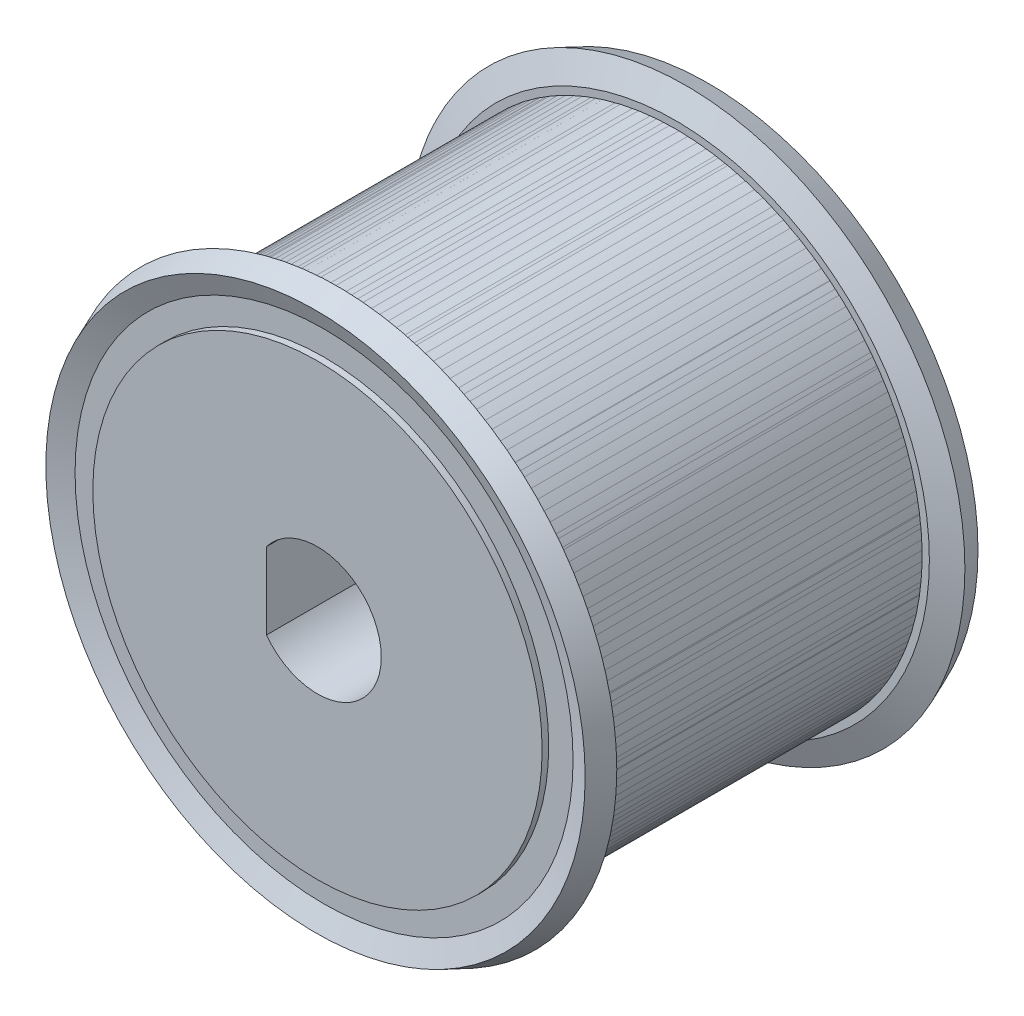
SolidWorks part; units mm, degrees
ref_plane "前视基准面" through (0, 0, 0) normal (0, 0, 1) x (1, 0, 0)
ref_plane "上视基准面" through (0, 0, 0) normal (0, 1, 0) x (1, 0, 0)
ref_plane "右视基准面" through (0, 0, 0) normal (1, 0, 0) x (0, 0, -1)
ref_axis "基准轴1" through (0, 0, 55) along (0, 0, -1)
sketch "SketchRevolveGearBelt01" plane through (0, 0, 0) normal (1, 0, 0) x (0, 0, -1)
  line L0 (0, 0) -> (1, 0) construction
  line L1 (15.24, 0) -> (15.24, 17.6084)
  line L2 (15.24, 17.6084) -> (14.7244, 17.6084)
  line L3 (14.7244, 17.6084) -> (14.7244, 19.5169)
  line L4 (14.7244, 19.5169) -> (15.3953, 21.1368)
  line L5 (15.3953, 21.1368) -> (13.6424, 21.8629)
  line L6 (13.6424, 21.8629) -> (12.827, 19.8944)
  line L7 (12.827, 19.8944) -> (12.827, 19.3229)
  line L8 (12.827, 19.3229) -> (-12.827, 19.3229)
  line L9 (-12.827, 19.3229) -> (-12.827, 19.8944)
  line L10 (-12.827, 19.8944) -> (-13.6424, 21.8629)
  line L11 (-13.6424, 21.8629) -> (-15.3953, 21.1368)
  line L12 (-15.3953, 21.1368) -> (-14.7244, 19.5169)
  line L13 (-14.7244, 19.5169) -> (-14.7244, 17.6084)
  line L14 (-14.7244, 17.6084) -> (-15.24, 17.6084)
  line L15 (-15.24, 17.6084) -> (-15.24, 0)
  line L16 (-15.24, 0) -> (15.24, 0)
  dimension "GearBeltFlange1OutsideLength" = 1.9086
  dimension "GearBeltFlange1X" = 0.6709
  dimension "GearBeltFlange1Y" = 1.6198
  dimension "GearBeltFlangeThickness" = 1.8974
  dimension "GearBeltFlangeInside" = 0.5715
  dimension "GearBeltOutsideDiameter" = 19.3229
  dimension "GearBeltFlange2X" = 0.6709
revolve "GearBelt01" add sketch "SketchRevolveGearBelt01" angle 360 about L0
sketch "SketchToothGearBelt01" plane through (0, 0, 0) normal (0, 0, 1) x (1, 0, 0)
  arc A0 (19.2019, 2.1549) -> (19.2019, -2.1549) centre (0, 0) cw
  spline S0 degree 3 poles (19.2019, -2.1549) (19.2051, -2.1266) (19.2062, -2.0838) (19.2007, -2.0271) (19.1929, -1.985) (19.1817, -1.9438) (19.167, -1.9037) (19.149, -1.8649) (19.1278, -1.8278) (19.1036, -1.7926) (19.0765, -1.7596) (19.0468, -1.7289) (19.0145, -1.7009) (18.9801, -1.6756) (18.9436, -1.6534) (18.9054, -1.6342) (18.8657, -1.6184) (18.8248, -1.6059) (18.7831, -1.597) (18.7407, -1.5914) (18.6735, -1.5892) (18.5873, -1.5911) (18.4822, -1.5873) (18.3832, -1.5753) (18.2854, -1.5557) (18.1895, -1.5285) (18.096, -1.4939) (18.0055, -1.452) (17.9186, -1.4032) (17.8357, -1.3477) (17.7575, -1.2859) (17.6843, -1.2181) (17.6167, -1.1449) (17.5551, -1.0665) (17.4997, -0.9836) (17.4511, -0.8965) (17.4094, -0.806) (17.3749, -0.7124) (17.3478, -0.6164) (17.3285, -0.5186) (17.3165, -0.4196) (17.313, -0.2999) (17.3145, -0.16) (17.3139, 0) (17.3145, 0.16) (17.313, 0.2999) (17.3165, 0.4196) (17.3285, 0.5186) (17.3478, 0.6164) (17.3749, 0.7124) (17.4094, 0.806) (17.4511, 0.8965) (17.4997, 0.9836) (17.5551, 1.0665) (17.6167, 1.1449) (17.6843, 1.2181) (17.7575, 1.2859) (17.8357, 1.3477) (17.9186, 1.4032) (18.0055, 1.452) (18.096, 1.4939) (18.1895, 1.5285) (18.2854, 1.5557) (18.3832, 1.5753) (18.4822, 1.5873) (18.5873, 1.5911) (18.6735, 1.5892) (18.7407, 1.5914) (18.7831, 1.597) (18.8248, 1.6059) (18.8657, 1.6184) (18.9054, 1.6342) (18.9436, 1.6534) (18.9801, 1.6756) (19.0145, 1.7009) (19.0468, 1.7289) (19.0765, 1.7596) (19.1036, 1.7926) (19.1278, 1.8278) (19.149, 1.8649) (19.167, 1.9037) (19.1817, 1.9438) (19.1929, 1.985) (19.2007, 2.0271) (19.2062, 2.0838) (19.2051, 2.1266) (19.2019, 2.1549) knots 0 0 0 0 0.013004 0.019506 0.026009 0.032511 0.039013 0.045515 0.052017 0.058519 0.065021 0.071524 0.078026 0.084528 0.09103 0.097532 0.104034 0.110536 0.117038 0.123541 0.130043 0.147745 0.16292 0.178095 0.19327 0.208445 0.223621 0.238796 0.253971 0.269146 0.284321 0.299496 0.314671 0.329846 0.345021 0.360196 0.375371 0.390546 0.405721 0.420897 0.436072 0.451247 0.475623 0.5 0.524377 0.548753 0.563928 0.579103 0.594279 0.609454 0.624629 0.639804 0.654979 0.670154 0.685329 0.700504 0.715679 0.730854 0.746029 0.761204 0.776379 0.791555 0.80673 0.821905 0.83708 0.852255 0.869957 0.876459 0.882962 0.889464 0.895966 0.902468 0.90897 0.915472 0.921974 0.928476 0.934979 0.941481 0.947983 0.954485 0.960987 0.967489 0.973991 0.980494 0.986996 1 1 1 1
extrude "ToothExtrudeCutGearBelt01" cut sketch "SketchToothGearBelt01" against normal blind 12.827 and the other way blind 12.827
pattern_circular "PatternGearBelt01" count 25 every 14.4 about axis through (0, 0, 55) along (0, 0, -1) of "ToothExtrudeCutGearBelt01"
sketch "草图6" plane through (0, 0, -15.24) normal (0, 0, -1) x (-1, 0, 0)
  circle A0 centre (0, 0) radius 14
  dimension "D1" = 28
extrude "切除-拉伸3" cut sketch "草图6" against normal blind 15
sketch "草图7" plane through (0, 0, -0.24) normal (0, 0, -1) x (-1, 0, 0)
  line L0 (4, 3) -> (4, -3)
  circle A0 centre (0, 0) radius 5
  dimension "D1" = 10
  dimension "D2" = 4
extrude "切除-拉伸4" cut sketch "草图7" against normal through all contours L0 A0 region at (0.2418, 0, -0.24)
